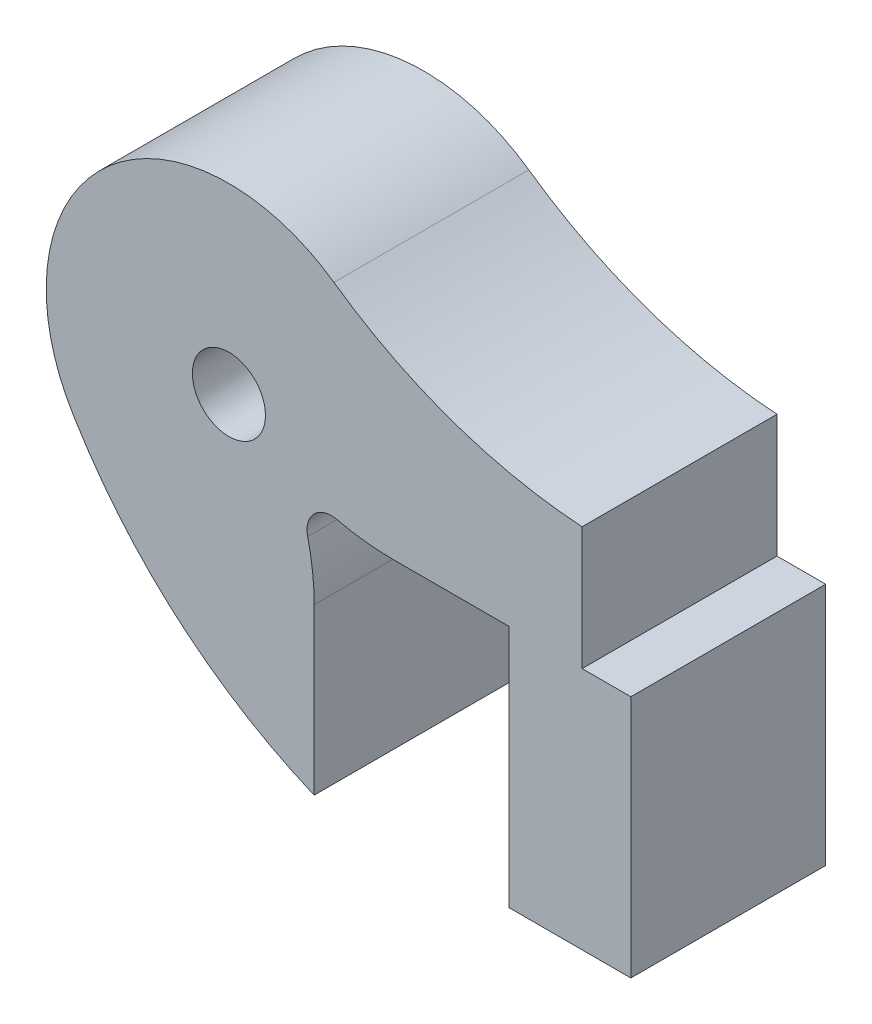
SolidWorks part; units mm, degrees
material "PMMA"
ref_plane "Front Plane" through (0, 0, 0) normal (0, 0, 1) x (1, 0, 0)
ref_plane "Top Plane" through (0, 0, 0) normal (0, 1, 0) x (1, 0, 0)
ref_plane "Right Plane" through (0, 0, 0) normal (1, 0, 0) x (0, 0, -1)
sketch "Sketch1" plane through (0, 0, 0) normal (0, 0, 1) x (1, 0, 0)
  line L0 (7, 10) -> (0, 15) construction
  line L1 (20, 0) -> (15, 0)
  line L2 (20, 0) -> (20, 15)
  line L3 (20, 15) -> (0, 15)
  line L4 (0, 0) -> (0, 15)
  line L7 (7, 0) -> (0, 0)
  line L9 (15, 0) -> (15, 10)
  line L10 (15, 10) -> (7, 10)
  line L11 (7, 0) -> (7, 10)
  circle A0 centre (3.5, 12.5) radius 1.5
  dimension "D3" = 3
  dimension "D1" = 20
  dimension "D2" = 5
  dimension "D4" = 10
  dimension "D5" = 8
  dimension "D6" = 5
extrude "Boss-Extrude1" add sketch "Sketch1" along normal blind 8
sketch "Sketch2" plane through (0, 0, 8) normal (0, 0, 1) x (1, 0, 0)
  line L0 (7, 10) -> (7.7071, 9.2929) construction
  line L1 (7, 0) -> (7, 10) construction
  line L3 (0, 0) -> (7, 0)
  line L4 (0, 0) -> (0, 1)
  line L5 (0, 1) -> (7, 1)
  line L6 (7, 0) -> (7, 1)
  circle A0 centre (7.7071, 9.2929) radius 1
  line M6 (7, 0) -> (7, 10)
  line M7 (7, 10) -> (15, 10)
  dimension "D1" = 2
  dimension "D2" = 45
  dimension "D3" = 1
extrude "Cut-Extrude1" cut sketch "Sketch2" against normal through all contours A0 M6 M7 | A0 region at (7.7988, 9.2012, 8)
fillet "Fillet1" radius 10 2 edges at (7, 8.5858, 4) (8.4142, 10, 4)
sketch "Sketch3" plane through (0, 0, 8) normal (0, 0, 1) x (1, 0, 0)
  circle A0 centre (3.5, 12.5) radius 7.5
  circle A1 centre (3.5, 12.5) radius 1.5 construction
  line M9 (20, 15) -> (0, 15)
  line M10 (0, 15) -> (0, 0)
  dimension "D1" = 15
extrude "Boss-Extrude2" add sketch "Sketch3" against normal blind 8 contours A0 M9 M10 region at (5.2855, 15.203, 8)
fillet "Fillet2" radius 20 2 edges at (10.5711, 15, 4) (0, 5.8668, 4)
fillet "Fillet3" radius 21 1 edges at (0, 0, 4)
sketch "Sketch4" plane through (0, 0, 8) normal (0, 0, 1) x (1, 0, 0)
  line L1 (20, 15.8569) -> (18, 15.8569)
  line L2 (20, 15.8569) -> (20, 10)
  line L3 (20, 10) -> (18, 10)
  line L4 (18, 15.8569) -> (18, 10)
  dimension "D1" = 2
  dimension "D2" = 5
extrude "Cut-Extrude2" cut sketch "Sketch4" against normal blind 10 contours L2 L3 L4 L1
